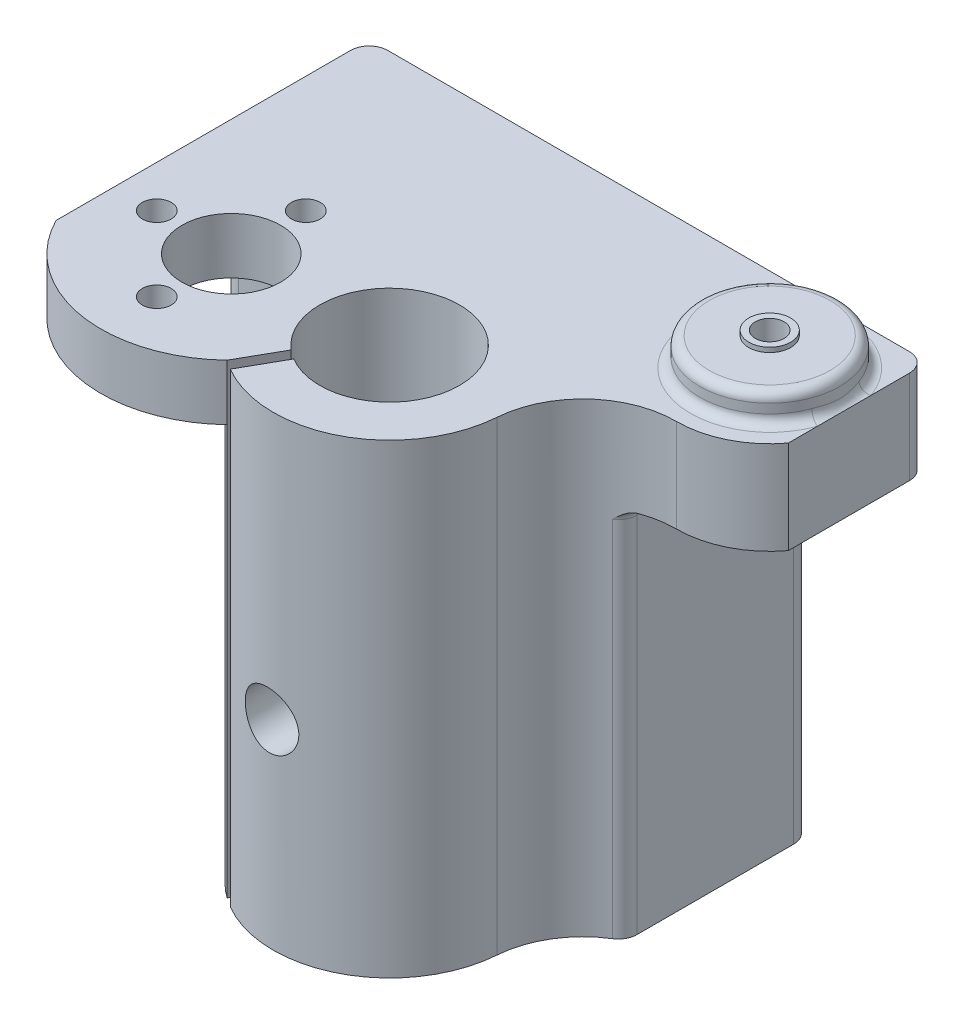
SolidWorks part; units mm, degrees
ref_plane "Alzado" through (0, 0, 0) normal (0, 0, 1) x (1, 0, 0)
ref_plane "Planta" through (0, 0, 0) normal (0, 1, 0) x (1, 0, 0)
ref_plane "Vista lateral" through (0, 0, 0) normal (1, 0, 0) x (0, 0, -1)
sketch "Croquis1" plane through (0, 0, 0) normal (0, 1, 0) x (1, 0, 0)
  line L0 (12.5, 22.7) -> (12.5, 6.7) construction
  line L1 (0, 42) -> (60, 42)
  line L2 (0, 42) -> (0, 0)
  line L3 (0, 0) -> (60, 0)
  line L4 (60, 42) -> (60, 0)
  line L5 (4.5, 14.7) -> (12.5, 14.7) construction
  circle A0 centre (29.5, 14.7) radius 7.5
  circle A1 centre (12.5, 14.7) radius 5.3
  circle A2 centre (12.5, 14.7) radius 8 construction
  circle A3 centre (12.5, 22.7) radius 1.55
  circle A4 centre (4.5, 14.7) radius 1.55
  circle A5 centre (12.5, 6.7) radius 1.55
  dimension "D3" = 15
  dimension "D4" = 10.6
  dimension "D6" = 17
  dimension "D7" = 12.5
  dimension "D9" = 16
  dimension "D10" = 3.1
  dimension "D1" = 60
  dimension "D2" = 42
  dimension "D5" = 14.7
  dimension "D8" = 14.7
extrude "Saliente-Extruir1" add sketch "Croquis1" along normal blind 50
sketch "Croquis2" plane through (0, 0, 0) normal (-1, 0, 0) x (0, 0, 1)
  line L0 (-42, 50) -> (0, 50) construction
  line L1 (-37, 27.3) -> (-29.25, 27.3)
  line L2 (-37, 27.3) -> (-37, 15)
  line L3 (-37, 15) -> (-29.25, 15)
  line L4 (-29.25, 27.3) -> (-29.25, 15)
  line L6 (-6.7, 50) -> (-6.7, 0) construction
  line L7 (-42, 0) -> (0, 0) construction
  line L8 (0, 50) -> (0, 0) construction
  dimension "D1" = 12.3
  dimension "D2" = 7.75
  dimension "D3" = 15
  dimension "D4" = 6.7
  dimension "D5" = 22.55
extrude "Cortar-Extruir1" cut sketch "Croquis2" against normal blind 41
sketch "Croquis3" plane through (0, 0, 0) normal (0, -1, 0) x (1, 0, 0)
  line L0 (60, -42) -> (0, -42) construction
  line L1 (0, 0) -> (20, 0)
  line L2 (0, 0) -> (0, -26)
  line L3 (0, -26) -> (20, -26)
  line L4 (20, 0) -> (20, -26)
  circle A0 centre (29.5, -14.7) radius 9.5 construction
  dimension "D1" = 19
  dimension "D2" = 16
extrude "Cortar-Extruir2" cut sketch "Croquis3" against normal blind 44
sketch "Croquis4" plane through (0, 0, -37) normal (0, 0, 1) x (1, 0, 0)
  line L0 (41, 27.3) -> (41, 15) construction
  line L1 (41, 15) -> (0, 15) construction
  circle A0 centre (29, 21.15) radius 1.55
  circle A1 centre (4, 21.15) radius 1.55
  dimension "D1" = 3.1
  dimension "D2" = 3.1
  dimension "D4" = 25
  dimension "D3" = 12
  dimension "D5" = 6.15
  dimension "D6" = 6.15
extrude "Cortar-Extruir3" cut sketch "Croquis4" against normal through all and the other way through all
sketch "Croquis6" plane through (0, 0, 0) normal (0, 0, 1) x (1, 0, 0)
  circle A0 centre (29, 21.15) radius 3
  dimension "D1" = 6
extrude "Cortar-Extruir4" cut sketch "Croquis6" against normal blind 26
sketch "Croquis7" plane through (0, 0, -42) normal (0, 0, -1) x (-1, 0, 0)
  line L1 (-0.6548, 20.9993) -> (-2.1968, 23.9717)
  line L2 (-25.6548, 20.9993) -> (-27.1968, 23.9717)
  line L3 (-27.1968, 23.9717) -> (-30.5421, 24.1224)
  line L4 (-30.5421, 24.1224) -> (-32.3452, 21.3007)
  line L5 (-32.3452, 21.3007) -> (-30.8032, 18.3283)
  line L6 (-30.8032, 18.3283) -> (-27.4579, 18.1776)
  line L7 (-27.4579, 18.1776) -> (-25.6548, 20.9993)
  line L8 (-2.1968, 23.9717) -> (-5.5421, 24.1224)
  line L9 (-5.5421, 24.1224) -> (-7.3452, 21.3007)
  line L10 (-7.3452, 21.3007) -> (-5.8032, 18.3283)
  line L11 (-5.8032, 18.3283) -> (-2.4579, 18.1776)
  line L12 (-2.4579, 18.1776) -> (-0.6548, 20.9993)
  circle A0 centre (-29, 21.15) radius 2.9 construction
  circle A1 centre (-4, 21.15) radius 2.9 construction
  dimension "D1" = 5.8
  dimension "D2" = 5.8
extrude "Cortar-Extruir5" cut sketch "Croquis7" against normal blind 2.5
sketch "Croquis8" plane through (0, 50, 0) normal (0, 1, 0) x (1, 0, 0)
  line L0 (60, 0) -> (60, 42) construction
  line L1 (60, 42) -> (0, 42) construction
  circle A0 centre (52, 33) radius 1.55
  dimension "D1" = 3.1
  dimension "D2" = 8
  dimension "D3" = 9
extrude "Cortar-Extruir6" cut sketch "Croquis8" against normal through all
sketch "Croquis9" plane through (0, 50, 0) normal (0, 1, 0) x (1, 0, 0)
  circle A0 centre (52, 33) radius 7.5
  circle A1 centre (52, 33) radius 1.55 construction
  circle A2 centre (52, 33) radius 1.55
  dimension "D1" = 15
extrude "Saliente-Extruir2" add sketch "Croquis9" along normal blind 3
sketch "Croquis11" plane through (0, 53, 0) normal (0, 1, 0) x (1, 0, 0)
  circle A0 centre (52, 33) radius 2.25
  circle A1 centre (52, 33) radius 1.55 construction
  circle A2 centre (52, 33) radius 1.55
  dimension "D1" = 4.5
extrude "Saliente-Extruir3" add sketch "Croquis11" along normal blind 0.5
sketch "Croquis14" plane through (0, 50, 0) normal (0, 1, 0) x (1, 0, 0)
  line L0 (0, 42) -> (0, 0) construction
  line L1 (0, 0) -> (60, 0) construction
  line L3 (60, 0) -> (60, 42) construction
  line L4 (0, 8.3952) -> (0, 0)
  line L5 (0, 0) -> (60, 0)
  line L7 (60, 0) -> (60, 39)
  arc A2 (51.9678, 23.0001) -> (60, 27) centre (52, 33) ccw
  arc A4 (0, 8.3952) -> (22.1691, 4.5754) centre (12.5, 14.7) ccw
  arc A5 (22.1691, 4.5754) -> (41.9643, 13.7556) centre (29.5, 14.7) ccw
  arc A6 (51.9678, 23.0001) -> (41.9643, 13.7556) centre (51.9357, 13.0001) ccw
  line M4 (0, 42) -> (0, 0)
  line M5 (0, 0) -> (60, 0)
  line M6 (60, 0) -> (60, 42)
  dimension "D1" = 14
  dimension "D2" = 12.5
  dimension "D4" = 20
  dimension "D5" = 20
extrude "Cortar-Extruir10" cut sketch "Croquis14" against normal up to surface (50 mm away) contours A2 A6 A5 A4 M4 M5 M6 region at (44.5854, 50, -9.0623) up to face at (52, 0, -31.45)
sketch "Croquis15" plane through (0, 0, 0) normal (0, -1, 0) x (1, 0, 0)
  line L0 (20, -26) -> (20, -2.8784) construction
  line L1 (20, -6.576) -> (20, -2.8784)
  arc A0 (22.1691, -4.5754) -> (20, -6.576) centre (29.5, -14.7) ccw
  arc A1 (41.9643, -13.7556) -> (22.1691, -4.5754) centre (29.5, -14.7) ccw construction
  arc A2 (22.1691, -4.5754) -> (20, -2.8784) centre (12.5, -14.7) ccw construction
  arc A3 (22.1691, -4.5754) -> (20, -2.8784) centre (12.5, -14.7) ccw
extrude "Cortar-Extruir11" cut sketch "Croquis15" against normal up to surface (44 mm away) up to face at (12.5, 44, -20)
sketch "Croquis17" plane through (0, 0, 0) normal (0, -1, 0) x (1, 0, 0)
  line L1 (60, -42) -> (47.5766, -42)
  line L2 (60, -42) -> (60, -22)
  line L3 (60, -22) -> (47.5766, -22)
  line L4 (47.5766, -42) -> (47.5766, -22)
  arc A0 (41.9643, -13.7556) -> (51.9678, -23.0001) centre (51.9357, -13.0001) ccw construction
  dimension "D1" = 20
extrude "Cortar-Extruir13" cut sketch "Croquis17" against normal blind 40
sketch "Croquis18" plane through (0, 40, 0) normal (0, -1, 0) x (1, 0, 0)
  circle A0 centre (52, -33) radius 3
  dimension "D1" = 6
extrude "Cortar-Extruir14" cut sketch "Croquis18" against normal blind 3.5
fillet "Redondeo1" radius 2 5 edges at (47.5766, 20, -22) (60, 45, -42) (47.5766, 20, -42) (0, 22, -26) (0, 25, -42)
fillet "Redondeo2" radius 1 2 edges at (52, 50, -25.5) (52, 53, -25.5)
fillet "Redondeo3" radius 1 6 edges at (0.5858, 44, -26.5858) (47.3258, 40, -22.207) (46.9908, 40, -41.4142) (11, 44, -26) (20, 44, -16.288) (47.5766, 40, -31.5883)
sketch "Croquis19" plane through (0, 50, 0) normal (0, 1, 0) x (1, 0, 0)
  line L0 (22.1691, 4.5754) -> (24.6561, 8.9741)
  line L1 (23.1759, 3.9178) -> (25.6372, 8.2712)
  circle A0 centre (29.5, 14.7) radius 7.5 construction
  arc A1 (22.1691, 4.5754) -> (41.9643, 13.7556) centre (29.5, 14.7) ccw construction
  circle A2 centre (12.5, 14.7) radius 5.3 construction
  arc A3 (24.6561, 8.9741) -> (25.6372, 8.2712) centre (29.5, 14.7) ccw
  arc A4 (22.1691, 4.5754) -> (23.1759, 3.9178) centre (29.5, 14.7) ccw
  dimension "D1" = 1.2
  dimension "D2" = 13.4
extrude "Cortar-Extruir15" cut sketch "Croquis19" against normal up to surface (50 mm away) up to face at (29.5, 0, -7.2)
